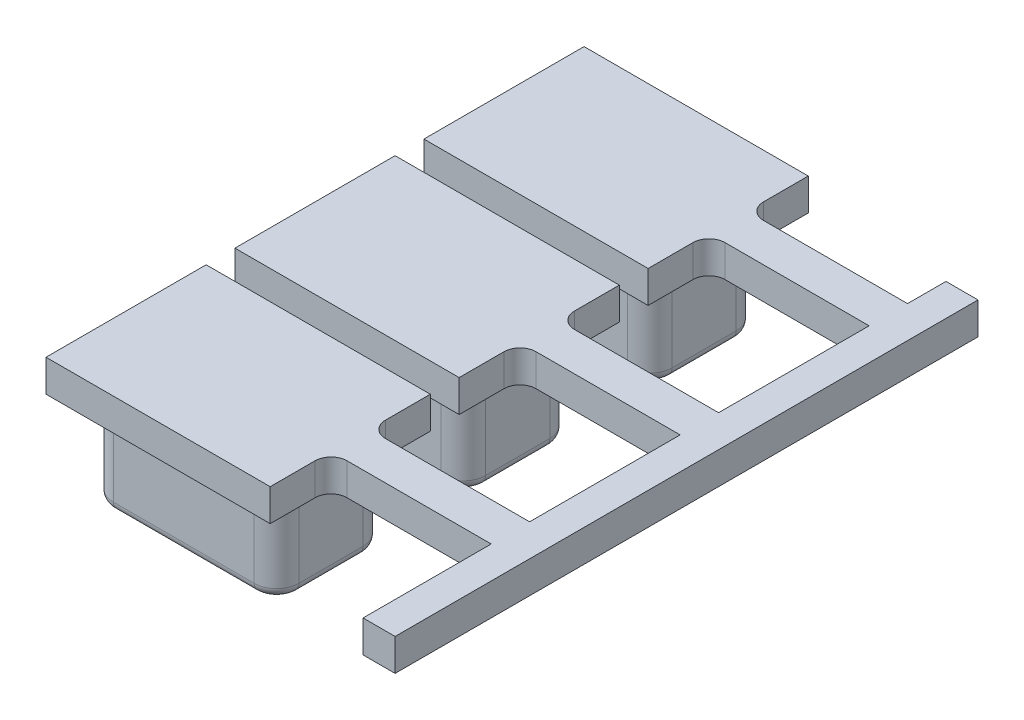
SolidWorks part; units mm, degrees
ref_plane "前视基准面" through (0, 0, 0) normal (0, 0, 1) x (1, 0, 0)
ref_plane "上视基准面" through (0, 0, 0) normal (0, 1, 0) x (1, 0, 0)
ref_plane "右视基准面" through (0, 0, 0) normal (1, 0, 0) x (0, 0, -1)
sketch "草图1" plane through (0, 0, 0) normal (0, 1, 0) x (1, 0, 0)
  line L0 (-2.2, 1.7) -> (2.2, 1.7)
  line L5 (-2.2, 7.5287) -> (2.2, 7.5287)
  line L6 (2.9, 6.8287) -> (2.9, 4.8287)
  line L7 (2.9, 1) -> (2.9, -1)
  line L8 (-2.2, -1.7) -> (2.2, -1.7)
  line L9 (-2.9, 1) -> (-2.9, -1)
  line L10 (-2.2, 4.1287) -> (2.2, 4.1287)
  line L11 (-2.9, 6.8287) -> (-2.9, 4.8287)
  line L12 (-2.2, 13.3491) -> (2.2, 13.3491)
  line L13 (2.9, 12.6491) -> (2.9, 10.6491)
  line L14 (-2.2, 9.9491) -> (2.2, 9.9491)
  line L15 (-2.9, 12.6491) -> (-2.9, 10.6491)
  arc A4 (2.2, 1.7) -> (2.9, 1) centre (2.2, 1) cw
  arc A5 (2.2, -1.7) -> (2.9, -1) centre (2.2, -1) ccw
  arc A6 (-2.9, -1) -> (-2.2, -1.7) centre (-2.2, -1) ccw
  arc A7 (-2.2, 1.7) -> (-2.9, 1) centre (-2.2, 1) ccw
  arc A8 (2.2, 7.5287) -> (2.9, 6.8287) centre (2.2, 6.8287) cw
  arc A9 (2.2, 4.1287) -> (2.9, 4.8287) centre (2.2, 4.8287) ccw
  arc A10 (-2.9, 4.8287) -> (-2.2, 4.1287) centre (-2.2, 4.8287) ccw
  arc A11 (-2.2, 7.5287) -> (-2.9, 6.8287) centre (-2.2, 6.8287) ccw
  arc A12 (2.2, 13.3491) -> (2.9, 12.6491) centre (2.2, 12.6491) cw
  arc A13 (2.2, 9.9491) -> (2.9, 10.6491) centre (2.2, 10.6491) ccw
  arc A14 (-2.9, 10.6491) -> (-2.2, 9.9491) centre (-2.2, 10.6491) ccw
  arc A15 (-2.2, 13.3491) -> (-2.9, 12.6491) centre (-2.2, 12.6491) ccw
  point P0 (0, 0)
  point P1 (-0.0497, 5.8287)
  point P15 (-0.0145, 11.6491)
  dimension "D1" = 3.4
  dimension "D2" = 5.8
extrude "凸台-拉伸1" add sketch "草图1" along normal blind 4
sketch "草图2" plane through (0, 4, 0) normal (0, 1, 0) x (1, 0, 0)
  line L1 (-3.4633, 14.2631) -> (3.5367, 14.2631)
  line L2 (-3.4633, 14.2631) -> (-3.4633, 9.2631)
  line L3 (-3.4633, 9.2631) -> (3.5367, 9.2631)
  line L4 (3.5367, 14.2631) -> (3.5367, 9.2631)
  line L5 (-3.4633, 8.3631) -> (3.5367, 8.3631)
  line L6 (-3.4633, 8.3631) -> (-3.4633, 3.3631)
  line L7 (-3.4633, 3.3631) -> (3.5367, 3.3631)
  line L8 (3.5367, 8.3631) -> (3.5367, 3.3631)
  line L9 (3.5367, 2.4631) -> (-3.4633, 2.4631)
  line L10 (3.5367, 2.4631) -> (3.5367, -2.5369)
  line L11 (3.5367, -2.5369) -> (-3.4633, -2.5369)
  line L12 (-3.4633, 2.4631) -> (-3.4633, -2.5369)
  dimension "D1" = 5
  dimension "D2" = 5
  dimension "D3" = 5
  dimension "D4" = 7
  dimension "D5" = 0.9
  dimension "D6" = 0.9
extrude "凸台-拉伸2" add sketch "草图2" against normal blind 1
sketch "草图3" plane through (0, 4, 0) normal (0, 1, 0) x (1, 0, 0)
  line L0 (3.5367, 9.2631) -> (3.5367, 14.2631) construction
  line L1 (3.5367, 12.3631) -> (9.5367, 12.3631)
  line L2 (3.5367, 12.3631) -> (3.5367, 11.1631)
  line L3 (3.5367, 11.1631) -> (9.5367, 11.1631)
  line L4 (9.5367, 12.3631) -> (9.5367, 11.1631)
  line L5 (3.5367, 3.3631) -> (3.5367, 8.3631) construction
  line L6 (3.5367, 6.4631) -> (9.5367, 6.4631)
  line L7 (3.5367, 6.4631) -> (3.5367, 5.2631)
  line L8 (3.5367, 5.2631) -> (9.5367, 5.2631)
  line L9 (9.5367, 6.4631) -> (9.5367, 5.2631)
  line L10 (3.5367, -2.5369) -> (3.5367, 2.4631) construction
  line L11 (3.5367, 0.5631) -> (9.5367, 0.5631)
  line L12 (3.5367, 0.5631) -> (3.5367, -0.6369)
  line L13 (3.5367, -0.6369) -> (9.5367, -0.6369)
  line L14 (9.5367, 0.5631) -> (9.5367, -0.6369)
  line L15 (-3.4633, 14.2631) -> (-3.4633, 9.2631) construction
  line L16 (-3.4633, 8.3631) -> (-3.4633, 3.3631) construction
  line L17 (-3.4633, 2.4631) -> (-3.4633, -2.5369) construction
  point P20 (-3.4633, 11.7631)
  point P21 (9.5367, 11.7631)
  point P24 (-3.4633, 5.8631)
  point P25 (9.5367, 5.8631)
  point P28 (-3.4633, -0.0369)
  point P29 (9.5367, -0.0369)
  dimension "D3" = 1.2
  dimension "D4" = 6
extrude "凸台-拉伸3" add sketch "草图3" against normal blind 1
sketch "草图4" plane through (0, 3, 0) normal (0, -1, 0) x (1, 0, 0)
  line L0 (3.5367, 0.6369) -> (9.5367, 0.6369) construction
  line L1 (9.5367, 0.6369) -> (8.5367, 0.6369)
  line L2 (9.5367, 0.6369) -> (9.5367, -12.3631)
  line L3 (9.5367, -12.3631) -> (8.5367, -12.3631)
  line L4 (8.5367, 0.6369) -> (8.5367, -12.3631)
  line L5 (9.5367, -12.3631) -> (3.5367, -12.3631) construction
  dimension "D1" = 1
extrude "凸台-拉伸4" add sketch "草图4" against normal blind 1
fillet "圆角1" radius 0.5 6 edges at (3.5367, 3.5, -12.3631) (3.5367, 3.5, -11.1631) (3.5367, 3.5, -5.2631) (3.5367, 3.5, -6.4631) (3.5367, 3.5, 0.6369) (3.5367, 3.5, -0.5631)
sketch "草图5" plane through (0, 0, -12.3631) normal (0, 0, -1) x (-1, 0, 0)
  line L0 (-4.0367, 4) -> (-9.5367, 4) construction
  line L1 (-9.5367, 3) -> (-8.5367, 3)
  line L2 (-9.5367, 3) -> (-9.5367, 4)
  line L3 (-9.5367, 4) -> (-8.5367, 4)
  line L4 (-8.5367, 3) -> (-8.5367, 4)
  dimension "D1" = 1
  dimension "D2" = 1
extrude "凸台-拉伸5" add sketch "草图5" along normal blind 1.2
fillet "圆角2" radius 0.3 24 edges at (2.695, 0, -13.1441) (2.9, 0, -11.6491) (2.695, 0, -10.1542) (0, 0, -9.9491) (-2.695, 0, -10.1542) (-2.9, 0, -11.6491) (-2.695, 0, -13.1441) (2.695, 0, -7.3237) (2.9, 0, -5.8287) (2.695, 0, -4.3337) (0, 0, -4.1287) (-2.695, 0, -4.3337) (-2.9, 0, -5.8287) (-2.695, 0, -7.3237) (2.695, 0, -1.495) (2.9, 0, 0) (2.695, 0, 1.495) (0, 0, 1.7) (-2.695, 0, 1.495) (-2.9, 0, 0) (-2.695, 0, -1.495) (0, 0, -13.3491) (0, 0, -7.5287) (0, 0, -1.7)
sketch "草图7" plane through (0, 0, 0.6369) normal (0, 0, 1) x (1, 0, 0)
  line L0 (4.0367, 4) -> (9.5367, 4) construction
  line L1 (9.5367, 3) -> (8.5367, 3)
  line L2 (9.5367, 3) -> (9.5367, 4)
  line L3 (9.5367, 4) -> (8.5367, 4)
  line L4 (8.5367, 3) -> (8.5367, 4)
  line L8 (9.5367, 3) -> (9.5367, 4) construction
  point P7 (0, 0)
  point P10 (0, 0)
  point P11 (8.5367, 3.4)
  point P12 (8.5367, 3.4)
  point P13 (0, 0)
  point P15 (0, 0)
  point P16 (9.5367, 3)
  point P21 (0, 0)
extrude "凸台-拉伸6" add sketch "草图7" along normal blind 4
